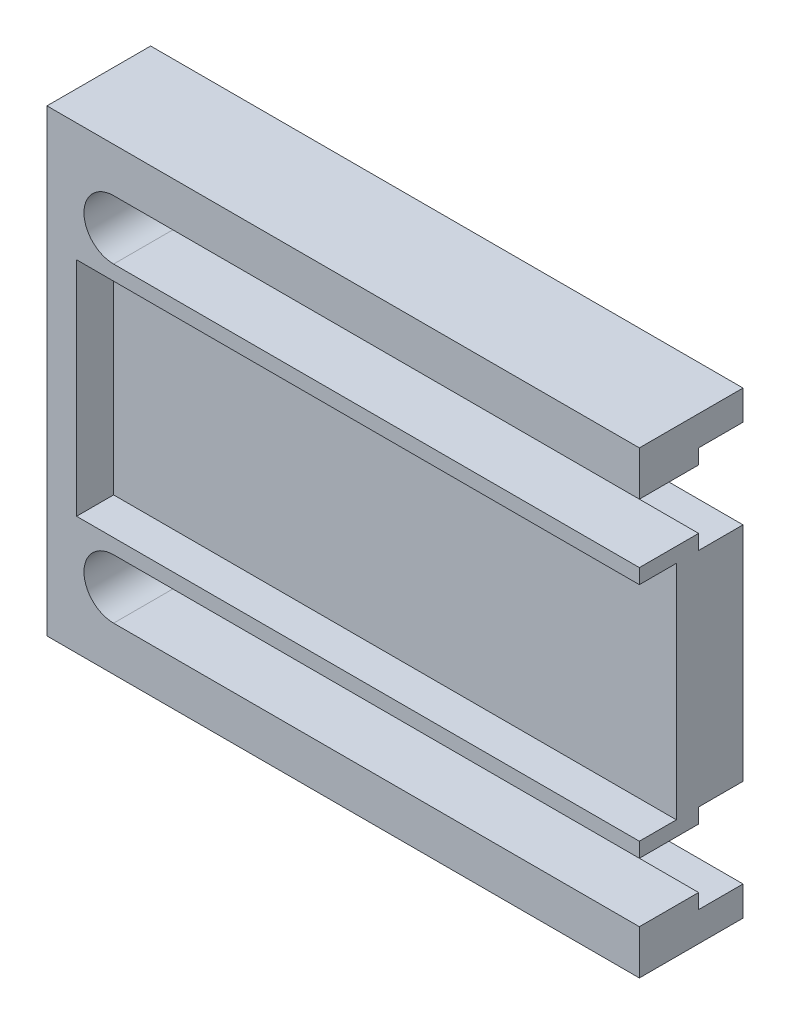
SolidWorks part; units mm, degrees
ref_plane "Front Plane" through (0, 0, 0) normal (0, 0, 1) x (1, 0, 0)
ref_plane "Top Plane" through (0, 0, 0) normal (0, 1, 0) x (1, 0, 0)
ref_plane "Right Plane" through (0, 0, 0) normal (1, 0, 0) x (0, 0, -1)
sketch "Sketch1" plane through (0, 0, 0) normal (0, 0, 1) x (1, 0, 0)
  line L0 (0, 24) -> (2.5, 24) construction
  line L1 (0, 0) -> (21, 0)
  line L2 (0, 0) -> (0, 21.5581)
  line L3 (0, 27) -> (21, 27)
  line L4 (21, 0) -> (21, 1)
  line L5 (6.5, 0) -> (14.5, 0)
  line L7 (6.5, 27) -> (14.5, 27)
  line L9 (0.75, 0) -> (5.75, 0)
  line L11 (0.75, 27) -> (5.75, 27)
  line L13 (21, 24) -> (18.5, 24) construction
  line L14 (15.25, 0) -> (20.25, 0)
  line L16 (15.25, 27) -> (20.25, 27)
  line L18 (0, 27) -> (21, 27)
  line L19 (0, 27) -> (0, 26)
  line L20 (0, 26) -> (21, 26)
  line L22 (0, 26) -> (21, 26)
  line L23 (0, 26) -> (0, 22)
  line L24 (0, 22) -> (21, 22)
  line L26 (21, 22) -> (0, 22)
  line L27 (21, 22) -> (21, 21)
  line L28 (21, 21) -> (0, 21)
  line L29 (0, 22) -> (0, 21)
  line L30 (0, 0) -> (21, 0)
  line L31 (0, 0) -> (0, 1)
  line L32 (0, 1) -> (21, 1)
  line L33 (21, 0) -> (21, 1)
  line L34 (0, 1) -> (21, 1)
  line L35 (0, 1) -> (0, 5)
  line L36 (0, 5) -> (21, 5)
  line L38 (0, 5) -> (21, 5)
  line L39 (0, 5) -> (0, 6)
  line L40 (0, 6) -> (21, 6)
  line L41 (21, 5) -> (21, 6)
  line L42 (2.5, 24) -> (18.5, 24) construction
  line L43 (10.5, 0) -> (10.5, -5.2941) construction
  line L44 (2.5, 26) -> (18.5, 26)
  line L45 (2.5, 22) -> (18.5, 22)
  line L46 (21, 13.5) -> (-10.3839, 13.5) construction
  line L47 (2.5, 3) -> (18.5, 3) construction
  line L48 (2.5, 1) -> (18.5, 1)
  line L49 (2.5, 5) -> (18.5, 5)
  line L50 (0, 0) -> (0, -2)
  line L51 (0, -2) -> (0, 0)
  line L52 (0, 0) -> (-2, 0)
  line L53 (-2, 0) -> (-2, -2)
  line L54 (21, 0) -> (23, 0)
  line L55 (-2, -2) -> (23, -2)
  line L56 (-2, -2) -> (-2, 29)
  line L57 (-2, 29) -> (23, 29)
  line L58 (23, -2) -> (23, 1)
  line L59 (21, 1) -> (23, 1)
  line L60 (21, 5) -> (23, 5)
  line L61 (21, 6) -> (23, 6)
  line L62 (21, 5) -> (21, 22)
  line L63 (23, 5) -> (23, 22)
  line L64 (21, 22) -> (23, 22)
  line L65 (21, 21) -> (23, 21)
  line L66 (21, 26) -> (23, 26)
  line L67 (21, 27) -> (23, 27)
  line L68 (23, 26) -> (23, 29)
  line L69 (23, 26) -> (23, 21.8489)
  line L70 (23, 5) -> (23, 1)
  arc A0 (2.5, 26) -> (2.5, 22) centre (2.5, 24) ccw
  arc A2 (2.5, 1) -> (2.5, 5) centre (2.5, 3) cw
  point P36 (10.5, 24)
  point P45 (10.5, 3)
  dimension "D3" = 31
  dimension "D4" = 25
  dimension "D1" = 27
  dimension "D2" = 21
  dimension "D9" = 1
  dimension "D10" = 4
  dimension "D11" = 1
  dimension "D12" = 1
  dimension "D13" = 4
  dimension "D14" = 1
extrude "IMU_Base" add sketch "Sketch1" along normal blind 7 contours L67 L68 L57 L56 L52 L2 L29 L23 L19 L3 | L55 L58 L54 L1 L50 | L53 L55 L50 L52 | L40 L62 L28 L2 | L65 L62 L61 L63 | L27 L65 L63 L64 | L24 L29 L2 L28 L27 L26 | L66 L68 L67 L3 L19 L20 L22 | L22 A0 L26 L24 L64 L69 L66 L20 | A0 L20 L23 L24 | L36 L38 L41 L40 L2 | L60 L63 L61 L41 | A2 L34 L32 L59 L70 L60 L36 L38 | L32 A2 L36 L2 | L32 L2 L1 L4 L34 | L59 L4 L54 L58 region at (10.5, 0.5, 0) region at (-1, 0.3829, 0) region at (11.5, -1, 0) region at (-1, -1, 0) region at (0.0472, 3, 0) region at (10.5, 5.5, 0) region at (11.9601, 3, 0) region at (10.5, 13.5, 0) region at (22, 0.5, 0) region at (10.5, 21.5, 0) region at (22, 5.5, 0) region at (22, 13.5, 0) region at (11.5, 26.5, 0) region at (22, 21.5, 0) region at (11.9601, 24, 0) region at (0.0472, 24, 0)
extrude "Screw_Channels" cut sketch "Sketch1<12>" along normal blind 14 contours L22 A0 L26 L24 L64 L69 L66 L20 | A2 L34 L32 L59 L70 L60 L36 L38 region at (11.9601, 3, 0) region at (11.9601, 24, 0)
sketch "Sketch1<12>" plane through (0, 0, 0) normal (0, 0, 1) x (1, 0, 0) same geometry as "Sketch1"
extrude "Nut_Channels" cut sketch "Sketch1<13>" along normal blind 3 contours L66 L68 L67 L3 L19 L20 L22 | A0 L20 L23 L24 | L24 L29 L2 L28 L27 L26 | L27 L65 L63 L64 | L60 L63 L61 L41 | L36 L38 L41 L40 L2 | L59 L4 L54 L58 | L32 L2 L1 L4 L34 | L32 A2 L36 L2 region at (10.5, 0.5, 0) region at (0.0472, 3, 0) region at (10.5, 5.5, 0) region at (22, 0.5, 0) region at (10.5, 21.5, 0) region at (22, 5.5, 0) region at (11.5, 26.5, 0) region at (22, 21.5, 0) region at (0.0472, 24, 0)
sketch "Sketch1<13>" plane through (0, 0, 0) normal (0, 0, 1) x (1, 0, 0) same geometry as "Sketch1"
sketch "Sketch2" plane through (0, 0, 7) normal (0, 0, 1) x (1, 0, 0)
  line L1 (0, 21) -> (23, 21)
  line L2 (0, 21) -> (0, 6)
  line L3 (0, 6) -> (23, 6)
  line L4 (23, 21) -> (23, 6)
extrude "Solder_Channels" cut sketch "Sketch2" against normal blind 2.5
sketch "Sketch4" plane through (23, 0, 0) normal (1, 0, 0) x (0, 0, -1)
  line L0 (-7, 26) -> (-7, 29)
  line L1 (-7, 29) -> (0, 29)
  line L2 (0, 29) -> (0, 27)
  line L3 (0, 27) -> (-3, 27)
  line L4 (-3, 26) -> (-7, 26)
  line L5 (-7, 22) -> (-3, 22)
  line L6 (-3, 22) -> (-3, 21)
  line L7 (-3, 21) -> (0, 21)
  line L8 (0, 21) -> (0, 6)
  line L9 (0, 6) -> (-3, 6)
  line L10 (-3, 6) -> (-3, 5)
  line L11 (-3, 5) -> (-7, 5)
  line L12 (-7, 5) -> (-7, 6)
  line L13 (-7, 6) -> (-4.5, 6)
  line L14 (-4.5, 6) -> (-4.5, 21)
  line L15 (-4.5, 21) -> (-7, 21)
  line L16 (-7, 21) -> (-7, 22)
  line L17 (-7, 1) -> (-3, 1)
  line L18 (-3, 1) -> (-3, 0)
  line L19 (-3, 0) -> (0, 0)
  line L20 (0, 0) -> (0, -2)
  line L21 (0, -2) -> (-7, -2)
  line L22 (-7, -2) -> (-7, 1)
  line L23 (-3, 27) -> (-3, 26)
extrude "IMU_Extension" add sketch "Sketch4" along normal blind 15
